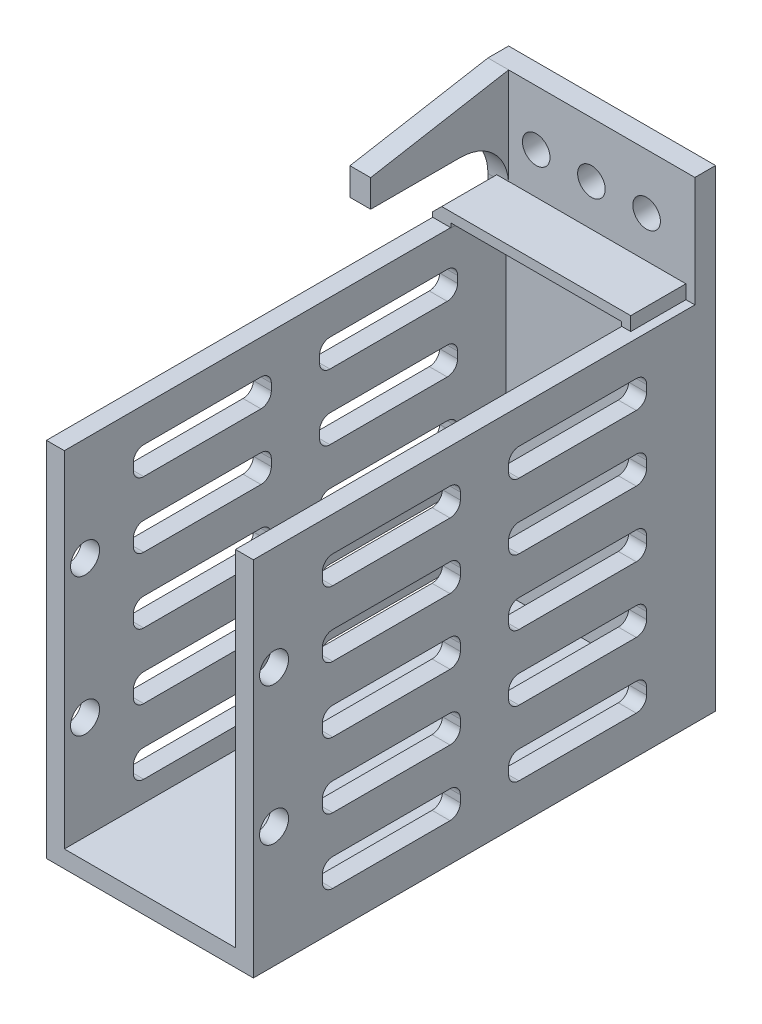
SolidWorks part; units mm, degrees
ref_plane "Front Plane" through (0, 0, 0) normal (0, 0, 1) x (1, 0, 0)
ref_plane "Top Plane" through (0, 0, 0) normal (0, 1, 0) x (1, 0, 0)
ref_plane "Right Plane" through (0, 0, 0) normal (1, 0, 0) x (0, 0, -1)
sketch "Sketch1" plane through (0, 0, 0) normal (0, 0, 1) x (1, 0, 0)
  line L0 (-72, -80.1107) -> (-72, -30.1107) construction
  line L2 (-72, -55.1107) -> (-72, -105.1107)
  line L3 (-72, -105.1107) -> (-42, -105.1107)
  line L4 (-42, -55.1107) -> (-42, -105.1107)
  line L5 (-42, -80.1107) -> (-42, -130.1107) construction
  line L6 (-72, -55.1107) -> (-72, -39.1107)
  line L7 (-72, -80.1107) -> (-72, -30.1107) construction
  line L8 (-42, -55.1107) -> (-42, -39.1107)
  line L9 (-42, -39.1107) -> (-72, -39.1107)
  line L11 (-72, -80.1107) -> (-40, -80.1107) construction
  dimension "D1" = 50
  dimension "D2" = 16
  dimension "D3" = 25
  dimension "D4" = 30
extrude "Boss-Extrude1" add sketch "Sketch1" along normal blind 3
sketch "Sketch2" plane through (0, 0, 3) normal (0, 0, 1) x (1, 0, 0)
  line L0 (-42, -105.1107) -> (-42, -39.1107) construction
  line L5 (-72, -39.1107) -> (-72, -105.1107) construction
  line L6 (-72, -105.1107) -> (-42, -105.1107) construction
  line L15 (-72, -55.1107) -> (-72, -105.1107)
  line L16 (-72, -105.1107) -> (-69.4, -105.1107)
  line L17 (-69.4, -55.1107) -> (-69.4, -105.1107)
  line L20 (-42, -105.1107) -> (-44.6, -105.1107)
  line L21 (-44.6, -55.1107) -> (-44.6, -105.1107)
  line L23 (-42, -55.1107) -> (-42, -105.1107)
  line L24 (-72, -55.1107) -> (-69.4, -55.1107)
  line L25 (-44.6, -55.1107) -> (-42, -55.1107)
  dimension "D1" = 24.8
  dimension "D2" = 50
extrude "Boss-Extrude2" add sketch "Sketch2" along normal blind 64
sketch "Sketch3" plane through (0, 0, 3) normal (0, 0, 1) x (1, 0, 0)
  line L0 (-72, -47.1107) -> (-42, -47.1107) construction
  line L1 (-72, -39.1107) -> (-72, -55.1107) construction
  line L2 (-42, -55.1107) -> (-42, -39.1107) construction
  circle A0 centre (-65, -47.1107) radius 2
  circle A1 centre (-57, -47.1107) radius 2
  circle A2 centre (-49, -47.1107) radius 2
  dimension "D1" = 4
  dimension "D2" = 4
  dimension "D3" = 4
  dimension "D4" = 8
  dimension "D5" = 8
extrude "Cut-Extrude1" cut sketch "Sketch3" against normal through all
sketch "Sketch4" plane through (0, -105.1107, 0) normal (0, -1, 0) x (1, 0, 0)
  line L1 (-72, 0) -> (-42, 0)
  line L2 (-72, 0) -> (-72, 67)
  line L3 (-72, 67) -> (-42, 67)
  line L4 (-42, 0) -> (-42, 67)
extrude "Boss-Extrude3" add sketch "Sketch4" along normal blind 2.5
sketch "Sketch5" plane through (-72, 0, 0) normal (-1, 0, 0) x (0, 0, 1)
  line L1 (55.5, -60.1107) -> (38.5, -60.1107)
  line L2 (57, -61.6107) -> (57, -62.6107)
  line L3 (55.5, -64.1107) -> (38.5, -64.1107)
  line L4 (37, -61.6107) -> (37, -62.6107)
  line L5 (67, -55.1107) -> (67, -107.6107) construction
  line L6 (67, -55.1107) -> (3, -55.1107) construction
  line L23 (33.5, -107.6107) -> (33.5, -55.1107) construction
  line L24 (67, -107.6107) -> (0, -107.6107) construction
  line L25 (57, -71.1107) -> (57, -72.1107)
  line L26 (55.5, -69.6107) -> (38.5, -69.6107)
  line L27 (37, -71.1107) -> (37, -72.1107)
  line L28 (55.5, -73.6107) -> (38.5, -73.6107)
  line L29 (57, -80.6107) -> (57, -81.6107)
  line L30 (55.5, -79.1107) -> (38.5, -79.1107)
  line L31 (37, -80.6107) -> (37, -81.6107)
  line L32 (55.5, -83.1107) -> (38.5, -83.1107)
  line L33 (57, -90.1107) -> (57, -91.1107)
  line L34 (55.5, -88.6107) -> (38.5, -88.6107)
  line L35 (37, -90.1107) -> (37, -91.1107)
  line L36 (55.5, -92.6107) -> (38.5, -92.6107)
  line L37 (57, -99.6107) -> (57, -100.6107)
  line L38 (55.5, -98.1107) -> (38.5, -98.1107)
  line L39 (37, -99.6107) -> (37, -100.6107)
  line L40 (55.5, -102.1107) -> (38.5, -102.1107)
  line L41 (11.5, -102.1107) -> (28.5, -102.1107)
  line L42 (30, -99.6107) -> (30, -100.6107)
  line L43 (11.5, -98.1107) -> (28.5, -98.1107)
  line L44 (10, -99.6107) -> (10, -100.6107)
  line L45 (11.5, -92.6107) -> (28.5, -92.6107)
  line L46 (30, -90.1107) -> (30, -91.1107)
  line L47 (11.5, -88.6107) -> (28.5, -88.6107)
  line L48 (10, -90.1107) -> (10, -91.1107)
  line L49 (11.5, -83.1107) -> (28.5, -83.1107)
  line L50 (30, -80.6107) -> (30, -81.6107)
  line L51 (11.5, -79.1107) -> (28.5, -79.1107)
  line L52 (10, -80.6107) -> (10, -81.6107)
  line L53 (11.5, -73.6107) -> (28.5, -73.6107)
  line L54 (30, -71.1107) -> (30, -72.1107)
  line L55 (11.5, -69.6107) -> (28.5, -69.6107)
  line L56 (10, -71.1107) -> (10, -72.1107)
  line L57 (30, -61.6107) -> (30, -62.6107)
  line L58 (11.5, -64.1107) -> (28.5, -64.1107)
  line L59 (10, -61.6107) -> (10, -62.6107)
  line L60 (11.5, -60.1107) -> (28.5, -60.1107)
  arc A0 (38.5, -64.1107) -> (37, -62.6107) centre (38.5, -62.6107) cw
  arc A1 (38.5, -60.1107) -> (37, -61.6107) centre (38.5, -61.6107) ccw
  arc A2 (57, -62.6107) -> (55.5, -64.1107) centre (55.5, -62.6107) cw
  arc A3 (55.5, -60.1107) -> (57, -61.6107) centre (55.5, -61.6107) cw
  arc A4 (55.5, -69.6107) -> (57, -71.1107) centre (55.5, -71.1107) cw
  arc A5 (57, -72.1107) -> (55.5, -73.6107) centre (55.5, -72.1107) cw
  arc A6 (38.5, -69.6107) -> (37, -71.1107) centre (38.5, -71.1107) ccw
  arc A7 (38.5, -73.6107) -> (37, -72.1107) centre (38.5, -72.1107) cw
  arc A8 (55.5, -79.1107) -> (57, -80.6107) centre (55.5, -80.6107) cw
  arc A9 (57, -81.6107) -> (55.5, -83.1107) centre (55.5, -81.6107) cw
  arc A10 (38.5, -79.1107) -> (37, -80.6107) centre (38.5, -80.6107) ccw
  arc A11 (38.5, -83.1107) -> (37, -81.6107) centre (38.5, -81.6107) cw
  arc A12 (55.5, -88.6107) -> (57, -90.1107) centre (55.5, -90.1107) cw
  arc A13 (57, -91.1107) -> (55.5, -92.6107) centre (55.5, -91.1107) cw
  arc A14 (38.5, -88.6107) -> (37, -90.1107) centre (38.5, -90.1107) ccw
  arc A15 (38.5, -92.6107) -> (37, -91.1107) centre (38.5, -91.1107) cw
  arc A16 (55.5, -98.1107) -> (57, -99.6107) centre (55.5, -99.6107) cw
  arc A17 (57, -100.6107) -> (55.5, -102.1107) centre (55.5, -100.6107) cw
  arc A18 (38.5, -98.1107) -> (37, -99.6107) centre (38.5, -99.6107) ccw
  arc A19 (38.5, -102.1107) -> (37, -100.6107) centre (38.5, -100.6107) cw
  arc A20 (28.5, -102.1107) -> (30, -100.6107) centre (28.5, -100.6107) ccw
  arc A21 (28.5, -98.1107) -> (30, -99.6107) centre (28.5, -99.6107) cw
  arc A22 (10, -100.6107) -> (11.5, -102.1107) centre (11.5, -100.6107) ccw
  arc A23 (11.5, -98.1107) -> (10, -99.6107) centre (11.5, -99.6107) ccw
  arc A24 (28.5, -92.6107) -> (30, -91.1107) centre (28.5, -91.1107) ccw
  arc A25 (28.5, -88.6107) -> (30, -90.1107) centre (28.5, -90.1107) cw
  arc A26 (10, -91.1107) -> (11.5, -92.6107) centre (11.5, -91.1107) ccw
  arc A27 (11.5, -88.6107) -> (10, -90.1107) centre (11.5, -90.1107) ccw
  arc A28 (28.5, -83.1107) -> (30, -81.6107) centre (28.5, -81.6107) ccw
  arc A29 (28.5, -79.1107) -> (30, -80.6107) centre (28.5, -80.6107) cw
  arc A30 (10, -81.6107) -> (11.5, -83.1107) centre (11.5, -81.6107) ccw
  arc A31 (11.5, -79.1107) -> (10, -80.6107) centre (11.5, -80.6107) ccw
  arc A32 (28.5, -73.6107) -> (30, -72.1107) centre (28.5, -72.1107) ccw
  arc A33 (28.5, -69.6107) -> (30, -71.1107) centre (28.5, -71.1107) cw
  arc A34 (10, -72.1107) -> (11.5, -73.6107) centre (11.5, -72.1107) ccw
  arc A35 (11.5, -69.6107) -> (10, -71.1107) centre (11.5, -71.1107) ccw
  arc A36 (11.5, -60.1107) -> (10, -61.6107) centre (11.5, -61.6107) ccw
  arc A37 (10, -62.6107) -> (11.5, -64.1107) centre (11.5, -62.6107) ccw
  arc A38 (28.5, -60.1107) -> (30, -61.6107) centre (28.5, -61.6107) cw
  arc A39 (28.5, -64.1107) -> (30, -62.6107) centre (28.5, -62.6107) ccw
  point P32 (37, -60.1107)
  point P35 (57, -64.1107)
  point P38 (57, -60.1107)
  dimension "D7" = 1.5
  dimension "D1" = 20
  dimension "D2" = 10
  dimension "D3" = 4
  dimension "D4" = 5
  dimension "D6" = 5.5
  dimension "D5" = 5
extrude "Cut-Extrude2" cut sketch "Sketch5" against normal through all
sketch "Sketch7" plane through (-72, 0, 0) normal (-1, 0, 0) x (0, 0, 1)
  line L0 (64, -55.1107) -> (64, -107.6107) construction
  line L1 (67, -55.1107) -> (3, -55.1107) construction
  line L2 (67, -107.6107) -> (0, -107.6107) construction
  line L3 (67, -55.1107) -> (67, -107.6107) construction
  circle A0 centre (64, -70.1107) radius 2.1
  circle A1 centre (64, -90.1107) radius 2.1
  dimension "D4" = 4.2
  dimension "D5" = 4.2
  dimension "D1" = 3
  dimension "D2" = 15
  dimension "D3" = 20
extrude "Cut-Extrude3" cut sketch "Sketch7" against normal through all
sketch "Sketch8" plane through (0, 0, 3) normal (0, 0, 1) x (1, 0, 0)
  line L0 (-57, -105.1107) -> (-57, -54.5107) construction
  line L1 (-44.6, -105.1107) -> (-69.4, -105.1107) construction
  line L2 (-57, -54.5107) -> (-69.3388, -54.5107) construction
  line L3 (-69.4, -55.1107) -> (-72, -55.1107) construction
  line L4 (-69.3388, -54.5107) -> (-44.6612, -54.5107)
  line L6 (-69.3388, -53.1107) -> (-44.6612, -53.1107)
  line L8 (-69.3388, -53.1107) -> (-70.7, -53.1107)
  line L9 (-69.3388, -54.5107) -> (-69.3388, -55.1107)
  line L10 (-69.3388, -55.1107) -> (-70.7, -55.1107)
  line L11 (-70.7, -53.1107) -> (-70.7, -55.1107)
  line L12 (-42, -55.1107) -> (-44.6, -55.1107) construction
  line L13 (-44.6612, -53.1107) -> (-43.3, -53.1107)
  line L14 (-44.6612, -54.5107) -> (-44.6612, -55.1107)
  line L15 (-44.6612, -55.1107) -> (-43.3, -55.1107)
  line L16 (-43.3, -53.1107) -> (-43.3, -55.1107)
  point P8 (-57, -54.5107)
  dimension "D1" = 50.6
  dimension "D2" = 1.4
  dimension "D3" = 24.6777
  dimension "D4" = 2
  dimension "D5" = 1.3612
extrude "Boss-Extrude4" add sketch "Sketch8" along normal blind 8
sketch "Sketch9" plane through (0, 0, 3) normal (0, 0, 1) x (1, 0, 0)
  line L0 (-72, -39.1107) -> (-72, -55.1107) construction
  line L1 (-72, -43.1107) -> (-69, -43.1107)
  line L2 (-72, -43.1107) -> (-72, -46.6107)
  line L3 (-72, -46.6107) -> (-69, -46.6107)
  line L4 (-69, -43.1107) -> (-69, -46.6107)
  dimension "D1" = 3
  dimension "D2" = 4
  dimension "D3" = 3.5
extrude "Boss-Extrude5" add sketch "Sketch9" along normal blind 20
chamfer "Chamfer1" distance 4 angle 80 1 edges at (-70.5, -43.1107, 3) first distance on face at (-63, -47.1107, 3)
fillet "Fillet1" radius 7 1 edges at (-70.5, -46.6107, 3)
chamfer "Chamfer2" distance 2 angle 45 1 edges at (-70.7, -55.1107, 7)
